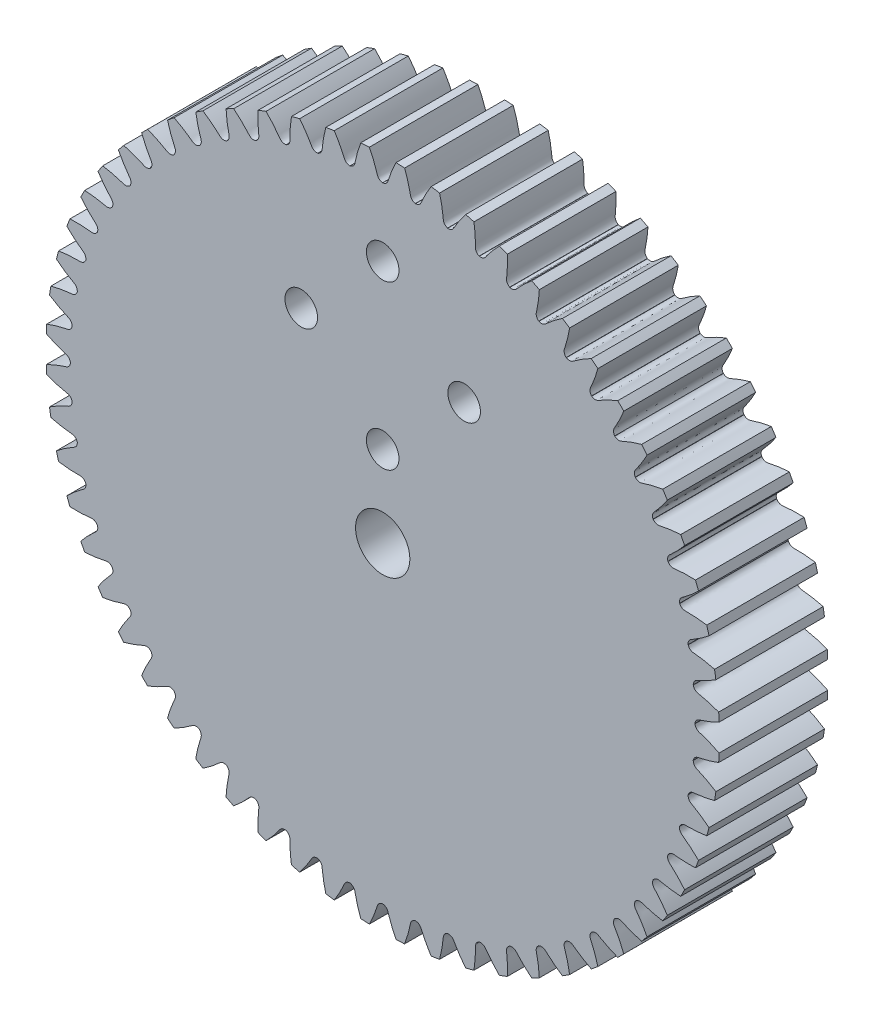
SolidWorks part; units mm, degrees
ref_plane "前视基准面" through (0, 0, 0) normal (0, 0, 1) x (1, 0, 0)
ref_plane "上视基准面" through (0, 0, 0) normal (0, 1, 0) x (1, 0, 0)
ref_plane "右视基准面" through (0, 0, 0) normal (1, 0, 0) x (0, 0, -1)
other "Configuration Table"
sketch "草图1" plane through (0, 0, 0) normal (0, 0, 1) x (1, 0, 0)
  circle A0 centre (0, 0) radius 31
extrude "凸台-拉伸1" add sketch "草图1" along normal blind 10
ref_axis "基准轴1" through (0, 0, -0.5) along (0, 0, 1)
sketch "草图2" plane through (0, 0, 0) normal (0, 0, 1) x (1, 0, 0)
  line L0 (0, 0) -> (0, 31) construction
  circle A0 centre (0, 0) radius 31 construction
  arc A1 (0.01, 28.75) -> (-0.01, 28.75) centre (0, 0) ccw
  arc A2 (4.2086, 35.0652) -> (-4.2086, 35.0652) centre (0, 0) ccw
  spline S0 degree 3 poles (0.01, 28.75) (0.4295, 28.8193) (0.4958, 29.1655) (0.6239, 29.5502) (0.684, 29.7232) (0.7519, 29.9052) (0.8274, 30.0965) (0.9111, 30.2965) (1.0033, 30.5052) (1.1044, 30.7222) (1.2149, 30.9473) (1.3349, 31.1801) (1.465, 31.4204) (1.6054, 31.6679) (1.7565, 31.9222) (1.9186, 32.183) (2.092, 32.45) (2.2771, 32.7228) (2.4741, 33.001) (2.6833, 33.2844) (2.905, 33.5724) (3.1395, 33.8647) (3.387, 34.1609) (3.7397, 34.5662) (4.0171, 34.8662) (4.2086, 35.0652) knots 0 0 0 0 0.112555 0.13496 0.158835 0.184181 0.210998 0.239286 0.269045 0.300275 0.332976 0.367147 0.40279 0.439904 0.478488 0.518544 0.56007 0.603067 0.647536 0.693475 0.740885 0.789766 0.840118 0.891941 1 1 1 1
  spline S1 degree 3 poles (-0.01, 28.75) (-0.4295, 28.8193) (-0.4958, 29.1655) (-0.6239, 29.5502) (-0.684, 29.7232) (-0.7519, 29.9052) (-0.8274, 30.0965) (-0.9111, 30.2965) (-1.0033, 30.5052) (-1.1044, 30.7222) (-1.2149, 30.9473) (-1.3349, 31.1801) (-1.465, 31.4204) (-1.6054, 31.6679) (-1.7565, 31.9222) (-1.9186, 32.183) (-2.092, 32.45) (-2.2771, 32.7228) (-2.4741, 33.001) (-2.6833, 33.2844) (-2.905, 33.5724) (-3.1395, 33.8647) (-3.387, 34.1609) (-3.7397, 34.5662) (-4.0171, 34.8662) (-4.2086, 35.0652) knots 0 0 0 0 0.112555 0.13496 0.158835 0.184181 0.210998 0.239286 0.269045 0.300275 0.332976 0.367147 0.40279 0.439904 0.478488 0.518544 0.56007 0.603067 0.647536 0.693475 0.740885 0.789766 0.840118 0.891941 1 1 1 1
extrude "切除-拉伸1" cut sketch "草图2" along normal through all
pattern_circular "阵列(圆周)1" count 60 every 6 about axis through (0, 0, -0.5) along (0, 0, 1) of "切除-拉伸1"
sketch "草图3" plane through (0, 0, 0) normal (0, 0, 1) x (1, 0, 0)
  circle A0 centre (0, 0) radius 30 construction
  dimension "Dn" = 60
sketch "草图4" plane through (0, 0, 10) normal (0, 0, 1) x (1, 0, 0)
  circle A0 centre (0, 15) radius 7.5 construction
  circle A1 centre (0, 22.5) radius 1.5
  circle A2 centre (7.5, 15) radius 1.5
  circle A3 centre (0, 7.5) radius 1.5
  circle A4 centre (-7.5, 15) radius 1.5
  point P14 (0, 15)
  dimension "D2" = 15
  dimension "D3" = 3
  dimension "D1" = 15
  dimension "D4" = 4
extrude "切除-拉伸2" cut sketch "草图4" against normal blind 10
sketch "草图5" plane through (0, 0, 10) normal (0, 0, 1) x (1, 0, 0)
  circle A0 centre (0, 0) radius 2.5
  dimension "D1" = 5
extrude "切除-拉伸3" cut sketch "草图5" against normal blind 10
